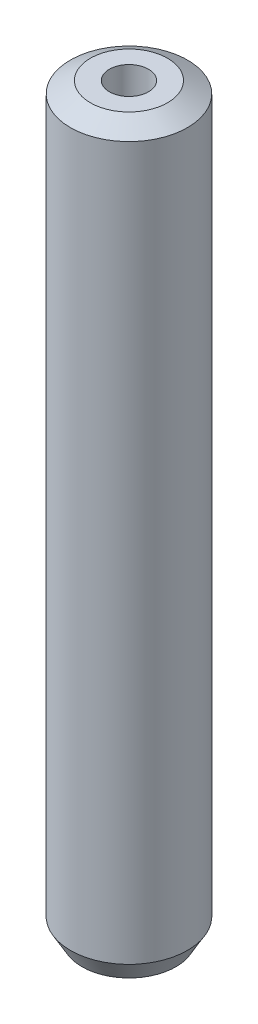
SolidWorks part; units mm, degrees
ref_plane "Front Plane" through (0, 0, 0) normal (0, 0, 1) x (1, 0, 0)
ref_plane "Top Plane" through (0, 0, 0) normal (0, 1, 0) x (1, 0, 0)
ref_plane "Right Plane" through (0, 0, 0) normal (1, 0, 0) x (0, 0, -1)
sketch "Sketch1" plane through (0, 0, 0) normal (0, 1, 0) x (1, 0, 0)
  circle A0 centre (0, 0) radius 30
  dimension "SHAFT_OD" = 60
extrude "Boss-Extrude1" add sketch "Sketch1" along normal blind 381.1601
sketch "Sketch2" plane through (0, 0, 0) normal (0, 1, 0) x (1, 0, 0)
  circle A0 centre (0, 0) radius 10.0376
  dimension "BORE_D" = 20.0752
extrude "Cut-Extrude1" cut sketch "Sketch2" along normal through all
chamfer "Chamfer1" distance 5.9037 angle 60 2 edges at (0, 381.1601, 30) (0, 0, 30) first distance on face at (0, 381.1601, 30) first distance on face at (0, 0, 10.0376)
